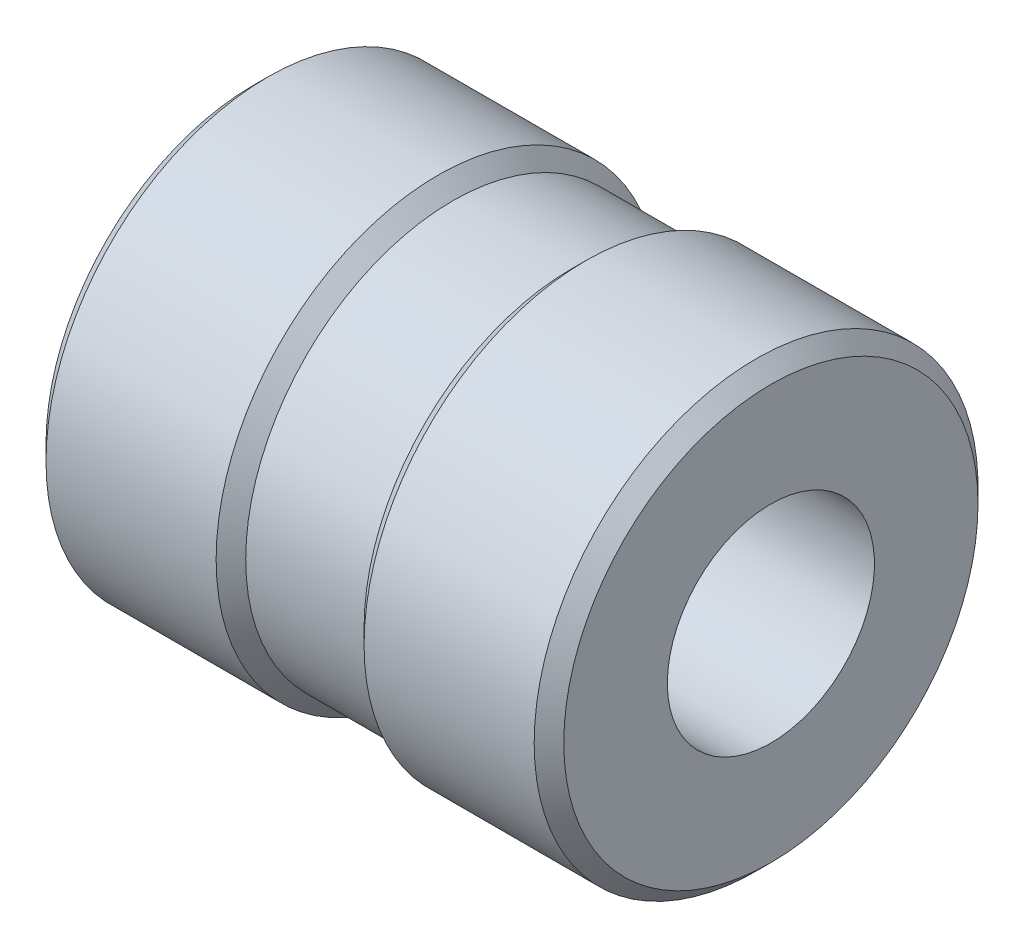
SolidWorks part; units mm, degrees
ref_plane "Płaszczyzna przednia" through (0, 0, 0) normal (0, 0, 1) x (1, 0, 0)
ref_plane "Płaszczyzna górna" through (0, 0, 0) normal (0, 1, 0) x (1, 0, 0)
ref_plane "Płaszczyzna prawa" through (0, 0, 0) normal (1, 0, 0) x (0, 0, -1)
sketch "Szkic1" plane through (0, 0, 0) normal (0, 0, 1) x (1, 0, 0)
  line L0 (0, 0) -> (14545.2504, 0) construction
  line L1 (-17.5, 15) -> (-17.5, 7)
  line L2 (-17.5, 7) -> (-3.5, 7)
  line L3 (17.5, 7) -> (17.5, 15)
  line L4 (17.5, 15) -> (4, 15)
  line L5 (0, 0) -> (0, 50000) construction
  line L6 (-3.5, 7) -> (-3.5, 2)
  line L7 (-3.5, 2) -> (3.5, 2)
  line L8 (3.5, 2) -> (3.5, 7)
  line L9 (3.5, 7) -> (17.5, 7)
  line L10 (-4, 15) -> (-4, 14)
  line L11 (4, 15) -> (4, 14)
  line L12 (-4, 14) -> (4, 14)
  line L13 (-4, 15) -> (-17.5, 15)
  dimension "D1" = 30
  dimension "D2" = 35
  dimension "D3" = 14
  dimension "D4" = 4
  dimension "D5" = 14
  dimension "D6" = 1
  dimension "D7" = 8
revolve "Obrót1" add sketch "Szkic1" angle 360 about L0
chamfer "Sfazowanie1" distance 1 angle 45 4 edges at (4, 0, 15) (-4, 0, 15) (-17.5, 0, 15) (17.5, 0, 15)
